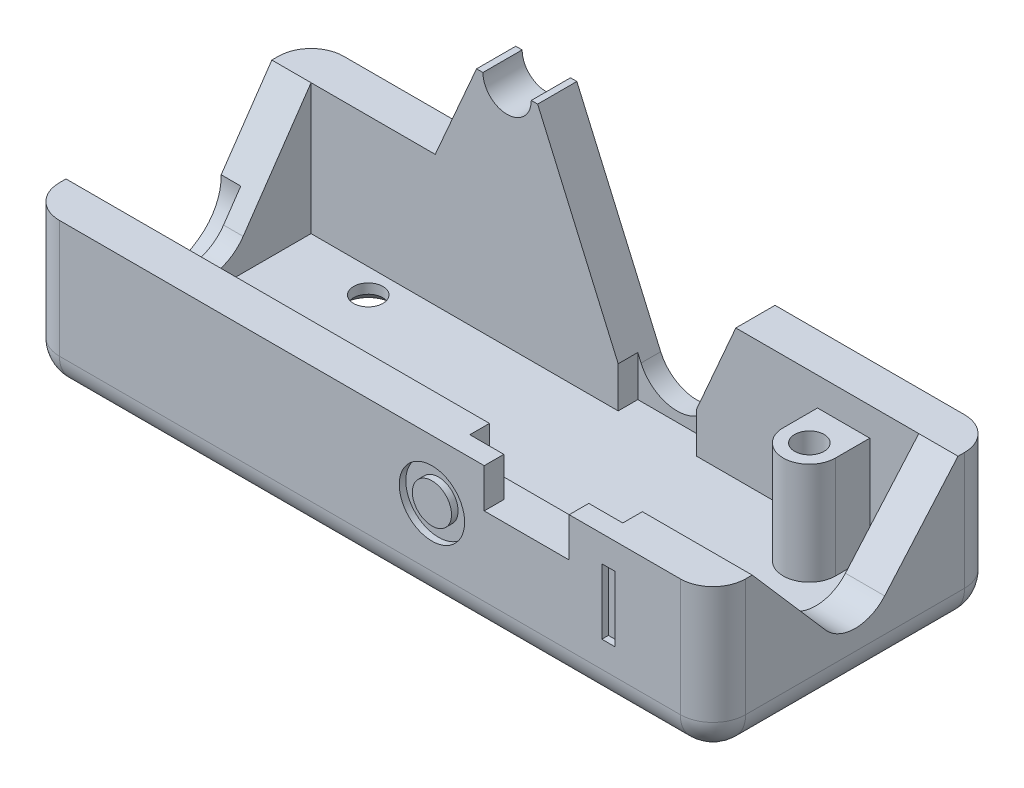
SolidWorks part; units mm, degrees
ref_plane "Front Plane" through (0, 0, 0) normal (0, 0, 1) x (1, 0, 0)
ref_plane "Top Plane" through (0, 0, 0) normal (0, 1, 0) x (1, 0, 0)
ref_plane "Right Plane" through (0, 0, 0) normal (1, 0, 0) x (0, 0, -1)
sketch "Sketch1" plane through (0, 0, 0) normal (0, 1, 0) x (1, 0, 0)
  line L0 (-26.25, -10.875) -> (26.25, -10.875)
  line L1 (-23.25, -7.75) -> (23.25, -7.75) construction
  line L2 (-23.25, -7.75) -> (-23.25, 7.75) construction
  line L3 (-23.25, 7.75) -> (23.25, 7.75) construction
  line L4 (23.25, -7.75) -> (23.25, 7.75) construction
  line L5 (-23.25, -7.75) -> (23.25, 7.75) construction
  line L6 (-23.25, 7.75) -> (23.25, -7.75) construction
  line L7 (26.25, -10.875) -> (26.25, 10.875)
  line L8 (-26.25, 10.875) -> (26.25, 10.875)
  line L9 (-26.25, -10.875) -> (-26.25, 10.875)
  line L10 (-17, -6) -> (-17, 6) construction
  line L11 (23.75, -10.875) -> (-23.75, -10.875) construction
  line L12 (-26.25, -8.375) -> (-26.25, 8.375) construction
  line L13 (26.25, 8.375) -> (26.25, -8.375) construction
  line L14 (-23.75, 10.875) -> (23.75, 10.875) construction
  circle A0 centre (-17, -6) radius 1.125 construction
  circle A1 centre (-17, 6) radius 1.125 construction
  circle A2 centre (17.5, 5.25) radius 1.25 construction
  point P0 (0, 0)
  dimension "D4" = 2.25
  dimension "D8" = 2.5
  dimension "D1" = 46.5
  dimension "D2" = 15.5
  dimension "D5" = 1.75
  dimension "D6" = 1.75
  dimension "D7" = 6.25
  dimension "D9" = 13
  dimension "D10" = 40.75
extrude "Boss-Extrude1" add sketch "Sketch1" along normal blind 1.5
sketch "Sketch2" plane through (0, 1.5, 0) normal (0, 1, 0) x (1, 0, 0)
  line L0 (23.25, 7.875) -> (-23.25, 7.875)
  line L1 (-23.25, 7.875) -> (-23.25, -7.875)
  line L2 (-23.25, -7.875) -> (23.25, -7.875)
  line L3 (23.25, -7.875) -> (23.25, 7.875)
  line L4 (23.25, 7.875) -> (9.25, 7.875) construction
  line L5 (-26.25, 10.875) -> (-26.25, -10.875)
  line L7 (-26.25, -10.875) -> (26.25, -10.875)
  line L12 (-26.25, 10.875) -> (26.25, 10.875) construction
  line L13 (26.25, -10.875) -> (26.25, 10.875)
  line L14 (26.25, -10.875) -> (26.25, 10.875) construction
  line L15 (26.25, 10.875) -> (-26.25, 10.875)
  line L16 (-26.25, -10.875) -> (26.25, -10.875) construction
  line L17 (-26.25, -10.875) -> (-26.25, 10.875) construction
  line L20 (-23.25, -7.75) -> (-23.25, 7.75) construction
  line L21 (23.25, -7.75) -> (23.25, 7.75) construction
  line L22 (17.85, -7.875) -> (23.25, -7.875) construction
extrude "Boss-Extrude2" add sketch "Sketch2" along normal blind 10
sketch "Sketch3" plane through (26.25, 0, 0) normal (1, 0, 0) x (0, 0, -1)
  line L3 (-3.9768, 7.0201) -> (3.9768, 7.0201) construction
  line L7 (0, 11.5) -> (0, 0) construction
  line L16 (-2.2631, 5.0508) -> (-7.875, 11.5)
  line L21 (-7.875, 11.5) -> (7.875, 11.5)
  line L23 (7.875, 11.5) -> (2.2631, 5.0508)
  line L25 (-10.875, 11.5) -> (10.875, 11.5) construction
  arc A0 (-2.2631, 5.0508) -> (2.2631, 5.0508) centre (0, 7.0201) ccw
  dimension "D4" = 3
  dimension "D1" = 6.4492
extrude "Cut-Extrude1" cut sketch "Sketch3" against normal up to surface (3 mm away)
sketch "Sketch4" plane through (0, 0, -10.875) normal (0, 0, -1) x (-1, 0, 0)
  line L0 (-26.25, 11.5) -> (26.25, 11.5) construction
  line L1 (2.75, 11.5) -> (-9.25, 11.5)
  line L3 (-3.25, 4.0503) -> (-5.9997, 4.0503) construction
  line L6 (-3.25, 3) -> (-3.25, 11.5) construction
  line L7 (-26.25, 11.5) -> (-26.25, 0) construction
  line L14 (-5.9997, 4.0503) -> (-9.25, 11.5)
  line L15 (-0.5003, 4.0503) -> (2.75, 11.5)
  arc A0 (-5.9997, 4.0503) -> (-0.5003, 4.0503) centre (-3.25, 5.25) ccw
  dimension "D3" = 3
  dimension "D1" = 6
  dimension "D2" = 6.25
  dimension "D4" = 23
  dimension "D5" = 7.4497
extrude "Cut-Extrude2" cut sketch "Sketch4" against normal blind 10
sketch "Sketch5" plane through (-26.25, 0, 0) normal (-1, 0, 0) x (0, 0, 1)
  line L3 (-3.9386, 5.75) -> (3.9386, 5.75) construction
  line L7 (0, 5.75) -> (0, 12.525) construction
  line L8 (5.5, 12.525) -> (-5.5, 12.525) construction
  line L17 (-2.6818, 3.9141) -> (-7.875, 11.5)
  line L23 (2.6818, 3.9141) -> (7.875, 11.5)
  line L24 (-7.875, 11.5) -> (7.875, 11.5)
  arc A0 (-2.6818, 3.9141) -> (2.6818, 3.9141) centre (0, 5.75) ccw
  dimension "D1" = 3.25
  dimension "D2" = 5.75
extrude "Cut-Extrude3" cut sketch "Sketch5" against normal up to surface (3 mm away) up to face at (-23.25, 6.5, 0)
fillet "Fillet1" radius 2.5 8 edges at (26.25, 5.75, 10.875) (-26.25, 5.75, 10.875) (-26.25, 5.75, -10.875) (26.25, 5.75, -10.875) (0, 0, 10.875) (-26.25, 0, 0) (0, 0, -10.875) (26.25, 0, 0)
sketch "Sketch6" plane through (0, 0, 10.875) normal (0, 0, 1) x (1, 0, 0)
  line L0 (-23.75, 11.5) -> (23.75, 11.5) construction
  line L1 (8.75, 11.5) -> (15.25, 11.5)
  line L2 (8.75, 11.5) -> (8.75, 8.5)
  line L3 (8.75, 8.5) -> (15.25, 8.5)
  line L4 (15.25, 11.5) -> (15.25, 8.5)
  line L7 (23.25, 11.5) -> (23.25, 1.5) construction
  dimension "D1" = 3
  dimension "D2" = 8
  dimension "D3" = 14.5
extrude "Cut-Extrude4" cut sketch "Sketch6" against normal up to surface (3 mm away) up to face at (0, 6.5, 7.875)
sketch "Sketch9" plane through (0, 0, 7.875) normal (0, 0, -1) x (-1, 0, 0)
  line L0 (23.25, 11.5) -> (-8.75, 11.5) construction
  line L1 (-17.85, 8.5) -> (-6.15, 8.5)
  line L2 (-17.85, 8.5) -> (-17.85, 11.5)
  line L3 (-17.85, 11.5) -> (-6.15, 11.5)
  line L4 (-6.15, 8.5) -> (-6.15, 11.5)
  line L5 (-15.25, 8.5) -> (-15.25, 11.5) construction
  dimension "D1" = 2.6
  dimension "D2" = 2.6
extrude "Cut-Extrude5" cut sketch "Sketch9" against normal blind 1.5
sketch "Sketch10" plane through (-26.25, 0, 0) normal (-1, 0, 0) x (0, 0, 1)
  circle A0 centre (0, 5.75) radius 4
  arc A1 (3.9701, 6.2385) -> (-3.9701, 6.2385) centre (0, 5.75) ccw construction
extrude "Cut-Extrude6" cut sketch "Sketch10" against normal blind 1.5
sketch "Sketch11" plane through (0, 0, -7.875) normal (0, 0, 1) x (1, 0, 0)
  line L0 (23.25, 1.5) -> (-23.25, 1.5) construction
  line L1 (0.25, 1.5) -> (6.25, 1.5)
  line L2 (0.25, 1.5) -> (0.25, 9.5)
  line L3 (0.25, 9.5) -> (6.25, 9.5)
  line L4 (6.25, 1.5) -> (6.25, 9.5)
  point P6 (3.25, 1.5)
  dimension "D1" = 6
  dimension "D2" = 8
extrude "Cut-Extrude7" cut sketch "Sketch11" against normal blind 1.5
sketch "Sketch14" plane through (0, 0, -10.875) normal (0, 0, 1) x (1, 0, 0)
  circle A0 centre (-8.25, 18.75) radius 1.6
  dimension "D1" = 3.2
  dimension "D2" = 11.5
  dimension "D3" = 13.5
sketch "Sketch15" plane through (0, 0, -10.875) normal (0, 0, -1) x (-1, 0, 0)
  circle A2 centre (8.25, 18.75) radius 1.85
  circle A3 centre (8.25, 18.75) radius 1.85
  dimension "D1" = 0.25
sketch "Sketch16" plane through (0, 0, -10.875) normal (0, 0, -1) x (-1, 0, 0)
  line L0 (2.75, 11.5) -> (5.9132, 18.75)
  line L1 (5.9132, 18.75) -> (6.4, 18.75)
  line L2 (-0.5003, 4.0503) -> (2.75, 11.5) construction
  line L3 (8.25, 18.75) -> (8.25, 11.5) construction
  line L4 (13.9137, 11.5) -> (23.75, 11.5) construction
  line L5 (13.75, 11.5) -> (10.5868, 18.75)
  line L6 (10.5868, 18.75) -> (10.1, 18.75)
  line L7 (2.75, 11.5) -> (13.75, 11.5)
  circle A0 centre (8.25, 18.75) radius 1.85 construction
  arc A1 (6.4, 18.75) -> (10.1, 18.75) centre (8.25, 18.75) ccw
extrude "Boss-Extrude3" add sketch "Sketch16" against normal up to vertex
sketch "Sketch17" plane through (0, 1.5, 0) normal (0, 1, 0) x (1, 0, 0)
  line L0 (15.5, 5.25) -> (15.5, 7.875)
  line L1 (23.25, 7.875) -> (6.25, 7.875) construction
  line L2 (19.5, 5.25) -> (19.5, 7.875)
  line L3 (15.5, 7.875) -> (19.5, 7.875)
  arc A0 (15.5, 5.25) -> (19.5, 5.25) centre (17.5, 5.25) ccw
  circle A1 centre (17.5, 5.25) radius 1.125
  point P1 (0, 0)
  point P10 (15, 5.25)
  dimension "D1" = 4
  dimension "D2" = 2.25
extrude "Boss-Extrude8" add sketch "Sketch17" along normal offset from surface (7.82 mm away) 2.18 up to face at (19.753, 11.5, -9.0446)
sketch "Sketch18" plane through (0, 0, 0) normal (0, -1, 0) x (1, 0, 0)
  circle A0 centre (17.5, -5.25) radius 1.125
  circle A1 centre (17.5, -5.25) radius 1.125 construction
extrude "Cut-Extrude10" cut sketch "Sketch18" against normal blind 2.18
sketch "Sketch19" plane through (0, 0, 0) normal (0, -1, 0) x (1, 0, 0)
  circle A0 centre (-17, 6) radius 1.125 construction
  circle A1 centre (-17, -6) radius 1.125 construction
  circle A2 centre (-17, 6) radius 1.125
  circle A3 centre (-17, -6) radius 1.125
extrude "Cut-Extrude11" cut sketch "Sketch19" against normal blind 2.18
chamfer "Chamfer1" distance 0.75 angle 45 3 edges at (17.5, 0, -6.375) (-17, 0, 4.875) (-17, 0, -7.125)
sketch "Sketch20" plane through (0, 0, 10.875) normal (0, 0, 1) x (1, 0, 0)
  line L0 (15.25, 11.5) -> (23.75, 11.5) construction
  line L1 (17.75, 4.5) -> (18.75, 4.5)
  line L2 (17.75, 4.5) -> (17.75, 9.5)
  line L3 (17.75, 9.5) -> (18.75, 9.5)
  line L4 (18.75, 4.5) -> (18.75, 9.5)
  line L5 (23.75, 2.5) -> (23.75, 11.5) construction
  circle A0 centre (4.75, 7) radius 2.5
  circle A1 centre (4.75, 7) radius 1.5
  point P11 (17.75, 7)
  dimension "D5" = 5
  dimension "D6" = 3
  dimension "D1" = 1
  dimension "D2" = 5
  dimension "D3" = 2
  dimension "D4" = 5
  dimension "D7" = 4
extrude "Cut-Extrude12" cut sketch "Sketch20" against normal blind 0.5
